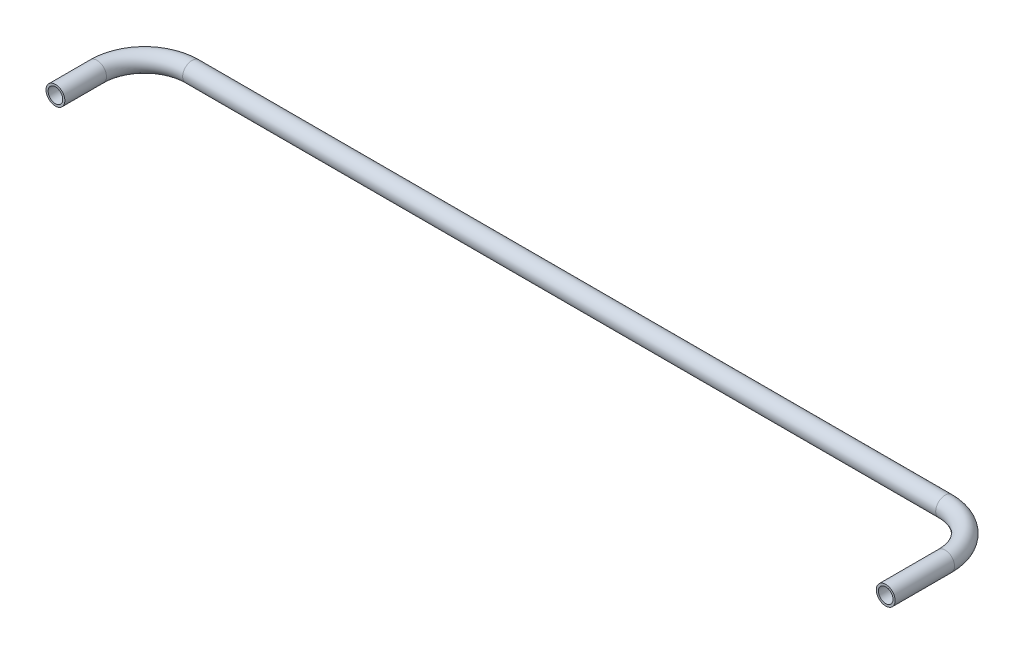
SolidWorks part; units mm, degrees
ref_plane "Front Plane" through (0, 0, 0) normal (0, 0, 1) x (1, 0, 0)
ref_plane "Top Plane" through (0, 0, 0) normal (0, 1, 0) x (1, 0, 0)
ref_plane "Right Plane" through (0, 0, 0) normal (1, 0, 0) x (0, 0, -1)
sketch "Sketch1" plane through (0, 0, 0) normal (0, 1, 0) x (1, 0, 0)
  line L0 (0, 0) -> (0, 14)
  line L1 (16, 30) -> (269.5, 30)
  line L2 (285.5, 14) -> (285.5, -6)
  arc A0 (269.5, 30) -> (285.5, 14) centre (269.5, 14) cw
  arc A1 (0, 14) -> (16, 30) centre (16, 14) cw
  dimension "D1" = 16
  dimension "D2" = 16
  dimension "D3" = 14
  dimension "D4" = 20
  dimension "D5" = 285.5
sketch "Sketch2" plane through (0, 0, 0) normal (0, 0, 1) x (1, 0, 0)
  circle A0 centre (0, 0) radius 3.175
  dimension "D1" = 6.35
sweep "Sweep-Thin1" add profiles "Sketch2" path "Sketch1" parameters "D1"=0.7112
